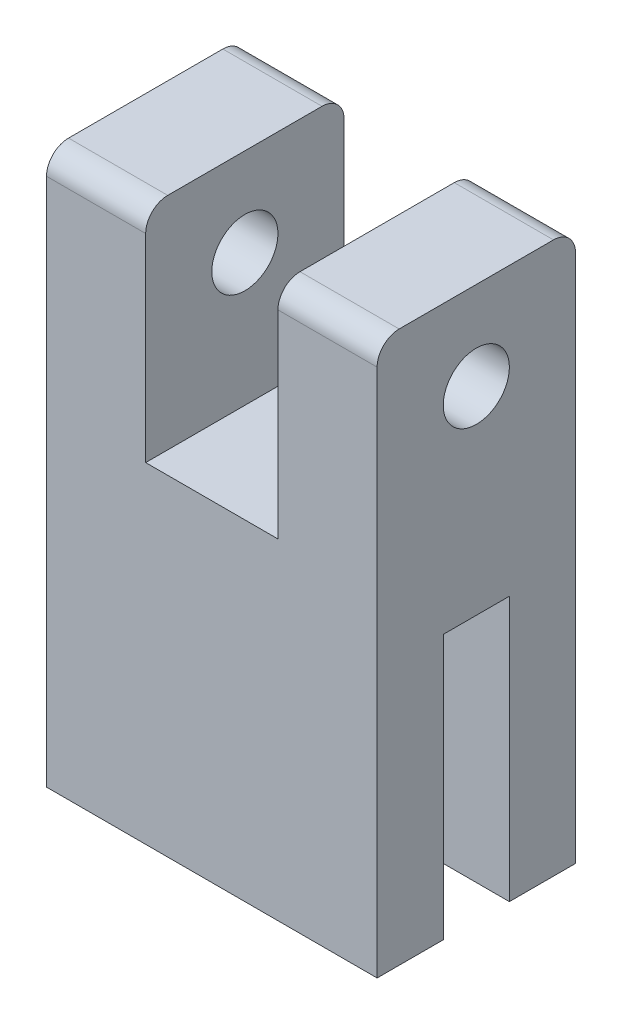
SolidWorks part; units mm, degrees
ref_plane "Alzado" through (0, 0, 0) normal (0, 0, 1) x (1, 0, 0)
ref_plane "Planta" through (0, 0, 0) normal (0, 1, 0) x (1, 0, 0)
ref_plane "Vista lateral" through (0, 0, 0) normal (1, 0, 0) x (0, 0, -1)
sketch "Croquis2" plane through (0, 0, 0) normal (0, 0, 1) x (1, 0, 0)
  line L1 (-7.5, 7.5) -> (7.5, 7.5)
  line L2 (-7.5, 7.5) -> (-7.5, -7.5)
  line L3 (-7.5, -7.5) -> (7.5, -7.5)
  line L4 (7.5, 7.5) -> (7.5, -7.5)
  point P4 (0, -7.5)
  point P6 (7.5, 0)
  dimension "D1" = 15
  dimension "D2" = 15
extrude "Saliente-Extruir1" add sketch "Croquis2" along normal mid plane 9
sketch "Croquis3" plane through (0, 0, 0) normal (0, 0, 1) x (1, 0, 0)
  line L0 (-7.5, 7.5) -> (-7.5, -7.5) construction
  line L1 (-7.5, 4.5) -> (7.5, 4.5)
  line L2 (-7.5, 4.5) -> (-7.5, -7.5)
  line L3 (-7.5, -7.5) -> (7.5, -7.5)
  line L4 (7.5, 4.5) -> (7.5, -7.5)
  line L5 (7.5, 7.5) -> (-7.5, 7.5) construction
  dimension "D1" = 3
extrude "Cortar-Extruir1" cut sketch "Croquis3" against normal mid plane 3
sketch "Croquis4" plane through (0, 0, 0) normal (0, 0, 1) x (1, 0, 0)
  line L0 (7.5, 7.5) -> (-7.5, 7.5) construction
  line L1 (-1.5, 1) -> (-1.5, -7.5)
  line L2 (-7.5, -7.5) -> (7.5, -7.5) construction
  line L3 (1.5, 1) -> (1.5, -7.5)
  line L4 (-1.5, -7.5) -> (1.5, -7.5)
  arc A0 (1.5, 1) -> (-1.5, 1) centre (0, 1) ccw
  dimension "D2" = 3
  dimension "D1" = 6.5
extrude "Cortar-Extruir2" cut sketch "Croquis4" against normal through all
sketch "Croquis10" plane through (0, 7.5, 0) normal (0, 1, 0) x (1, 0, 0)
  line L0 (-3, 4.5) -> (-3, -4.5)
  line L1 (3, 4.5) -> (3, -4.5)
  line L2 (0, 4.5) -> (0, -4.5) construction
  line L3 (-3, 4.5) -> (-7.5, 4.5)
  line L4 (7.5, 4.5) -> (-7.5, 4.5)
  line L5 (-7.5, 4.5) -> (-7.5, -4.5)
  line L6 (-7.5, -4.5) -> (7.5, -4.5)
  line L7 (7.5, -4.5) -> (7.5, 4.5)
  line L8 (7.5, 4.5) -> (3, 4.5)
  line L9 (-7.5, 4.5) -> (-7.5, -4.5)
  line L10 (-7.5, -4.5) -> (-3, -4.5)
  line L11 (7.5, -4.5) -> (7.5, 4.5)
  line L12 (3, -4.5) -> (7.5, -4.5)
  line L13 (7.5, 4.5) -> (-7.5, 4.5) construction
  point P11 (0, 0)
  dimension "D2" = 6
  dimension "D1" = 0
extrude "Saliente-Extruir4" add sketch "Croquis10" along normal blind 10
sketch "Croquis7" plane through (0, 0, 0) normal (1, 0, 0) x (0, 0, -1)
  line L1 (-4.5, 17.5) -> (4.5, 17.5) construction
  circle A0 centre (0, 13.5) radius 1.5
  dimension "D1" = 3
  dimension "D2" = 4
extrude "Cortar-Extruir3" cut sketch "Croquis7" against normal through all both and the other way through all
fillet "Redondeo2" radius 1 4 edges at (5.25, 17.5, -4.5) (5.25, 17.5, 4.5) (-5.25, 17.5, 4.5) (-5.25, 17.5, -4.5)
